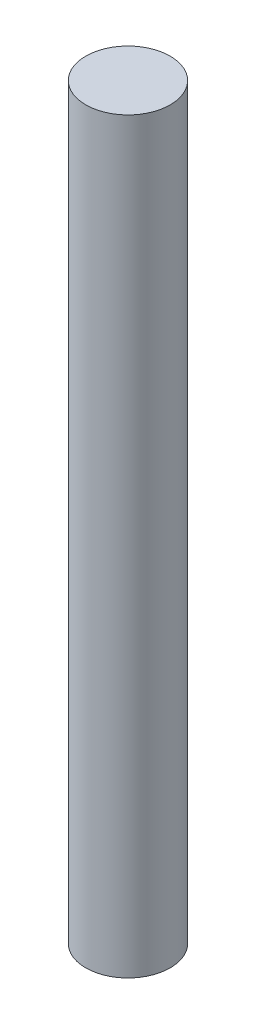
SolidWorks part; units mm, degrees
ref_plane "Alzado" through (0, 0, 0) normal (0, 0, 1) x (1, 0, 0)
ref_plane "Planta" through (0, 0, 0) normal (0, 1, 0) x (1, 0, 0)
ref_plane "Vista lateral" through (0, 0, 0) normal (1, 0, 0) x (0, 0, -1)
sketch "Croquis1" plane through (0, 0, 0) normal (0, 1, 0) x (1, 0, 0)
  circle A0 centre (0, 0) radius 4
  dimension "D1" = 8
extrude "Saliente-Extruir1" add sketch "Croquis1" along normal blind 100
ref_plane "Plano1" through (-3.1949, 0, 2.4067) normal (-0.7987, 0, 0.6017) x (0.6017, 0, 0.7987)
ref_plane "Plano2" through (-3.1949, 0, 2.4067) normal (-0.7987, 0, 0.6017) x (0.6017, 0, 0.7987)
sketch "Croquis2" plane through (-3.1949, 0, 2.4067) normal (-0.7987, 0, 0.6017) x (0.6017, 0, 0.7987)
  line L7 (-8.8187, 29.1961) -> (9.15, 29.1961)
  line L8 (-8.8187, 29.1961) -> (-8.8187, -2.457)
  line L9 (-8.8187, -2.457) -> (9.15, -2.457)
  line L10 (9.15, 29.1961) -> (9.15, -2.457)
extrude "Cortar-Extruir1" cut sketch "Croquis2" against normal blind 23
